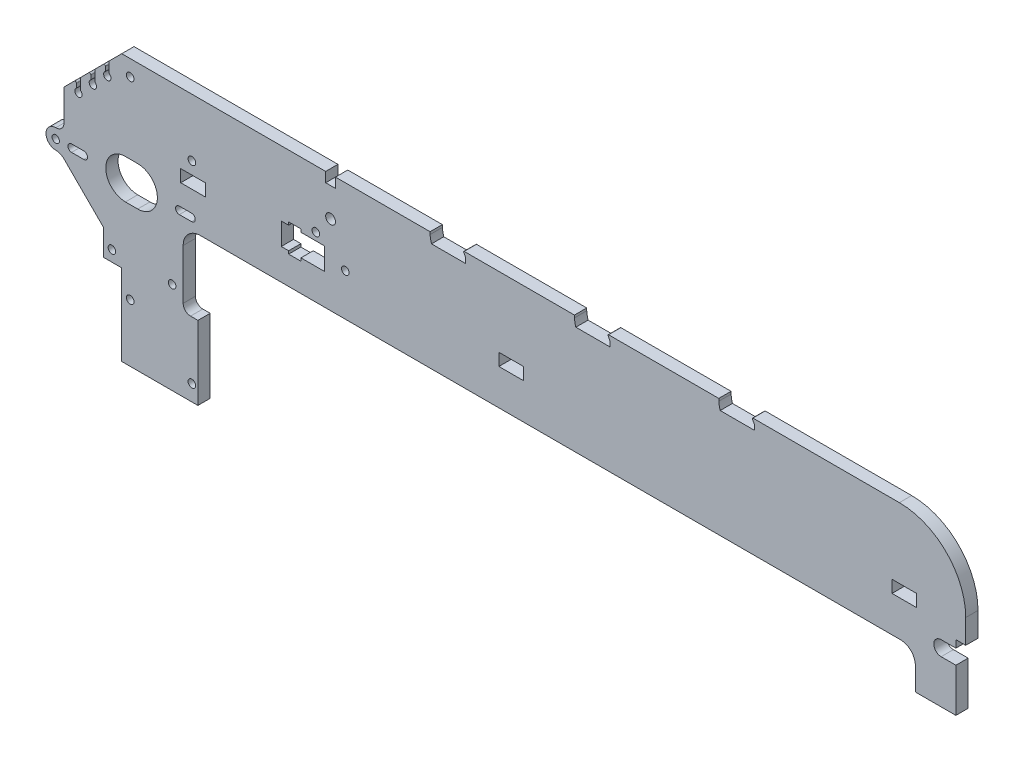
SolidWorks part; units mm, degrees
material "6061-T6 Black anodised"
ref_plane "Front Plane" through (0, 0, 0) normal (0, 0, 1) x (1, 0, 0)
ref_plane "Top Plane" through (0, 0, 0) normal (0, 1, 0) x (1, 0, 0)
ref_plane "Right Plane" through (0, 0, 0) normal (1, 0, 0) x (0, 0, -1)
sketch "Sketch1" plane through (0, 0, 0) normal (0, 0, 1) x (1, 0, 0)
  line L0 (-19.5, 0) -> (36.1968, 0) construction
  line L1 (-1.5, 32) -> (20.5, 32) construction
  line L2 (-21.9203, 0) -> (-30, 0) construction
  line L3 (-6.5, 43.5) -> (-6.5, 28.8553) construction
  line L4 (-1.5, 43.5) -> (20.5, 43.5) construction
  line L5 (310, 43.5) -> (250.4045, 43.5)
  line L6 (21.9203, 0) -> (0, 21.9203) construction
  line L7 (0, 21.9203) -> (-21.9203, 0) construction
  line L8 (-21.9203, 0) -> (0, -21.9203) construction
  line L9 (0, -21.9203) -> (21.9203, 0) construction
  line L10 (316.5, -4.6) -> (316.5, -20)
  line L11 (-6.5, -65) -> (-6.5, -32)
  line L12 (-30, 5.3553) -> (-30, -5.3553) construction
  line L13 (327, 3.7) -> (333, 3.7)
  line L14 (316.5, -20) -> (333, -20)
  line L15 (18.5, -4.6) -> (316.5, -4.6)
  line L16 (34.5, -11.1) -> (59.432, -11.1) construction
  line L17 (333, 6.7) -> (333, 3.7)
  line L18 (9.5, 43.5) -> (9.5, -35.4767) construction
  line L19 (-1.5, 43.5) -> (20.5, 43.5) construction
  line L20 (-1.5, 43.5) -> (-1.5, 20.5) construction
  line L21 (-6.5, -65) -> (24.5, -65)
  line L22 (-1.5, 20.5) -> (20.5, 20.5) construction
  line L23 (327, -2.3) -> (333, -2.3)
  line L24 (333, -2.3) -> (333, -20)
  line L25 (333, 6.7) -> (337, 6.7)
  line L26 (337, 6.7) -> (337, 16.5)
  line L27 (18.5, -35) -> (18.5, -4.6)
  line L28 (20.5, 43.5) -> (20.5, 20.5) construction
  line L29 (17.5, 15) -> (17.5, 10)
  line L30 (17.5, 15) -> (27.5, 15)
  line L31 (27, 72.5933) -> (67, 72.5933) construction
  line L32 (147, 10) -> (157, 10)
  line L33 (147, 10) -> (147, 15)
  line L34 (17.5, 10) -> (27.5, 10)
  line L35 (27.5, 15) -> (27.5, 10)
  line L36 (147, 15) -> (157, 15)
  line L37 (157, 10) -> (157, 15)
  line L38 (307, 10) -> (317, 10)
  line L39 (307, 10) -> (307, 15)
  line L40 (307, 15) -> (317, 15)
  line L41 (317, 10) -> (317, 15)
  line L42 (27, 72.5933) -> (27, -81.6129) construction
  line L43 (27, -81.6129) -> (67, -81.6129) construction
  line L44 (67, 72.5933) -> (67, -81.6129) construction
  line L45 (-1.5, -52.5) -> (20.5, -52.5) construction
  line L46 (-1.5, -65) -> (20.5, -65) construction
  line L47 (-1.5, -65) -> (-1.5, -42) construction
  line L48 (-1.5, -42) -> (20.5, -42) construction
  line L49 (20.5, -65) -> (20.5, -42) construction
  line L50 (58.4277, 8) -> (61.4277, 8)
  line L51 (27.5, 12.5) -> (63.9277, 12.5) construction
  line L52 (61.4277, 6.8061) -> (66.4277, 6.8061)
  line L53 (61.4277, 6.8061) -> (61.4277, 8)
  line L54 (76, 8) -> (76, 17)
  line L55 (72.5, 20.1) -> (72.5, 7.1) construction
  line L56 (66.4277, 6.8061) -> (66.4277, 8)
  line L57 (66.4277, 8) -> (76, 8)
  line L58 (63.9277, 12.5) -> (76, 12.5) construction
  line L59 (66.4277, 18.1939) -> (61.4277, 18.1939)
  line L60 (66.4277, 6.8061) -> (61.4277, 18.1939) construction
  line L61 (61.4277, 6.8061) -> (66.4277, 18.1939) construction
  line L62 (18.5, -35) -> (24.5, -35)
  line L63 (66.4277, 17) -> (66.4277, 18.1939)
  line L64 (66.4277, 17) -> (76, 17)
  line L65 (61.4277, 17) -> (61.4277, 18.1939)
  line L66 (24.5, -35) -> (24.5, -65)
  line L67 (-14, -21.3553) -> (-30, -5.3553)
  line L68 (-14, -21.3553) -> (-14, -32)
  line L69 (-14, -32) -> (-6.5, -32)
  line L70 (119, 43.5) -> (119, 42.5)
  line L71 (119.5675, 39.5) -> (133.5, 39.5)
  line L72 (177.75, 43.5) -> (177.75, 42.5)
  line L73 (119, 43.5) -> (80.5, 43.5)
  line L74 (-6.5, 28.8553) -> (-30, 5.3553) construction
  line L75 (178.3175, 39.5) -> (192.25, 39.5)
  line L76 (159.788, -14) -> (-14, -14) construction
  line L77 (159.788, -14) -> (159.788, -26) construction
  line L78 (61.4277, 17) -> (58.4277, 17)
  line L79 (159.788, -26) -> (-14, -26) construction
  line L80 (-14, -14) -> (-14, -26) construction
  line L81 (58.4277, 17) -> (58.4277, 8)
  line L82 (159.788, -14) -> (-14, -26) construction
  line L83 (159.788, -26) -> (-14, -14) construction
  line L84 (192.25, 39.5) -> (192.25, 41.5)
  line L85 (192.25, 41.5) -> (191.4309, 43.1382)
  line L86 (236.5, 43.5) -> (236.5, 42.5)
  line L87 (237.0675, 39.5) -> (251, 39.5)
  line L88 (251, 39.5) -> (251, 41.5)
  line L89 (177.75, 43.5) -> (132.9045, 43.5)
  line L90 (251, 41.5) -> (250.1809, 43.1382)
  line L91 (-33.3631, 8.7185) -> (-33.3631, -8.7185) construction
  line L92 (76.5, 27.7514) -> (80.5, 27.7514) construction
  line L93 (133.5, 39.5) -> (133.5, 41.5)
  line L94 (76.5, 43.5) -> (76.5, 39.5)
  line L95 (76.5, 39.5) -> (80.5, 39.5)
  line L96 (80.5, 43.5) -> (80.5, 39.5)
  line L97 (76.5, 43.5) -> (-6.5, 43.5)
  line L98 (-30, 20) -> (-6.5, 43.5)
  line L99 (-30, 20) -> (-30, 7.3254)
  line L100 (133.5, 41.5) -> (132.6809, 43.1382)
  line L101 (119, 43.5) -> (177.75, 43.5) construction
  line L102 (191.6545, 43.5) -> (236.5, 43.5)
  circle A0 centre (9.5, 34.5) radius 1.55 construction
  circle A1 centre (0, 0) radius 15.5 construction
  circle A2 centre (0, 21.9203) radius 1.5 construction
  circle A3 centre (21.9203, 0) radius 1.5
  circle A4 centre (0, -21.9203) radius 1.5 construction
  circle A5 centre (-21.9203, 0) radius 1.5
  circle A6 centre (0, 0) radius 5.5 construction
  arc A7 (337, 16.5) -> (310, 43.5) centre (310, 16.5) ccw
  circle A8 centre (0, 0) radius 8
  circle A9 centre (-3.05, 37) radius 1.55
  circle A10 centre (9.5, -57) radius 1.55 construction
  arc A11 (327, 3.7) -> (327, -2.3) centre (327, 0.7) ccw
  circle A12 centre (72, 0.4) radius 5 construction
  circle A13 centre (22, 38.5) radius 5 construction
  circle A14 centre (22, 38.5) radius 1.5 construction
  circle A15 centre (72, 0.4) radius 1.5 construction
  circle A16 centre (22.05, 20) radius 1.55
  circle A17 centre (-3.05, -41.5) radius 1.55
  circle A18 centre (22.05, -58.5) radius 1.55
  circle A19 centre (81.5, 20.1) radius 1.55 construction
  circle A20 centre (72.5, 20.1) radius 1.55
  circle A21 centre (84.5, 12.5) radius 1.55
  circle A22 centre (-10.5, -27.55) radius 1.55
  arc A23 (-33.3631, 3.9623) -> (-33.3631, -3.9623) centre (-33.3631, 0) ccw
  circle A24 centre (14, -27.55) radius 1.55
  circle A25 centre (-33.3631, 0) radius 1.5
  arc A26 (-33.3631, 3.9623) -> (-30, 7.3254) centre (-33.3631, 7.3254) ccw
  arc A27 (-33.3631, -3.9623) -> (-30, -5.3553) centre (-33.3631, -8.7185) cw
  circle A28 centre (78.5, 27.7514) radius 2
  arc A29 (119, 42.5) -> (119.5675, 39.5) centre (132.5, 43.5) ccw
  arc A30 (132.9045, 43.5) -> (132.6809, 43.1382) centre (132.9045, 43.25) ccw
  arc A31 (177.75, 42.5) -> (178.3175, 39.5) centre (191.25, 43.5) ccw
  arc A32 (191.6545, 43.5) -> (191.4309, 43.1382) centre (191.6545, 43.25) ccw
  arc A33 (236.5, 42.5) -> (237.0675, 39.5) centre (250, 43.5) ccw
  arc A34 (250.4045, 43.5) -> (250.1809, 43.1382) centre (250.4045, 43.25) ccw
  point P18 (26.8692, -2.8293)
  point P19 (26.8692, 2.8293)
  point P108 (58.4277, 12.5)
  point P115 (72.894, -20)
  dimension "D2" = 31
  dimension "D3" = 3
  dimension "D4" = 11
  dimension "D12" = 16
  dimension "D20" = 3.1
  dimension "D22" = 8
  dimension "D25" = 3
  dimension "D28" = 6
  dimension "D32" = 10
  dimension "D38" = 3
  dimension "D14" = 31
  dimension "D41" = 3.1
  dimension "D44" = 9
  dimension "D45" = 3.1
  dimension "D53" = 6
  dimension "D18" = 7.5
  dimension "D57" = 3.1
  dimension "D69" = 4
  dimension "D65" = 0.5
  dimension "D7" = 9
  dimension "D11" = 16.5
  dimension "D17" = 15
  dimension "D8" = 65
  dimension "D9" = 43.5
  dimension "D5" = 9.5
  dimension "D6" = 4.6
  dimension "D10" = 6.5
  dimension "D13" = 337
  dimension "D15" = 23
  dimension "D16" = 25
  dimension "D19" = 30
  dimension "D21" = 9
  dimension "D23" = 21.1
  dimension "D24" = 15.4
  dimension "D26" = 6
  dimension "D27" = 4
  dimension "D29" = 67
  dimension "D30" = 17.5
  dimension "D31" = 40
  dimension "D33" = 5
  dimension "D34" = 10
  dimension "D35" = 20
  dimension "D36" = 180
  dimension "D37" = 22
  dimension "D39" = 5
  dimension "D40" = 12
  dimension "D42" = 11
  dimension "D43" = 6
  dimension "D46" = 3.1
  dimension "D47" = 9
  dimension "D48" = 15
  dimension "D49" = 0.7
  dimension "D50" = 5
  dimension "D51" = 12
  dimension "D52" = 3.5
  dimension "D54" = 4
  dimension "D55" = 12
  dimension "D56" = 20
  dimension "D58" = 4.5
  dimension "D59" = 3
  dimension "D60" = 9
  dimension "D61" = 30
  dimension "D62" = 12.5
  dimension "D63" = 1
  dimension "D64" = 14.5
  dimension "D66" = 1
  dimension "D68" = 4
  dimension "D70" = 6
  dimension "D71" = 2
  dimension "D72" = 58.75
  dimension "D67" = 3
extrude "Boss-Extrude1" add sketch "Sketch1" along normal blind 5
fillet "Fillet1" [suppressed] radius 8
fillet "Fillet2" radius 7 1 edges at (18.5, -4.6, 2.5)
fillet "Fillet3" radius 3 1 edges at (18.5, -35, 2.5)
sketch "Sketch2" plane through (0, 0, 5) normal (0, 0, 1) x (1, 0, 0)
  line L0 (21.9203, 0) -> (16.9203, 0) construction
  line L1 (21.9203, -1.5) -> (16.9203, -1.5)
  line L2 (21.9203, 1.5) -> (16.9203, 1.5)
  line L3 (0, 0) -> (-5, 0) construction
  line L4 (0, -8) -> (-5, -8)
  line L5 (0, 8) -> (-5, 8)
  line L6 (-21.9203, 0) -> (-26.9203, 0) construction
  line L7 (-21.9203, -1.5) -> (-26.9203, -1.5)
  line L8 (-21.9203, 1.5) -> (-26.9203, 1.5)
  arc A0 (21.9203, -1.5) -> (21.9203, 1.5) centre (21.9203, 0) ccw
  arc A1 (16.9203, 1.5) -> (16.9203, -1.5) centre (16.9203, 0) ccw
  arc A2 (0, -8) -> (0, 8) centre (0, 0) ccw
  arc A3 (-5, 8) -> (-5, -8) centre (-5, 0) ccw
  arc A4 (-21.9203, -1.5) -> (-21.9203, 1.5) centre (-21.9203, 0) ccw
  arc A5 (-26.9203, 1.5) -> (-26.9203, -1.5) centre (-26.9203, 0) ccw
  circle A6 centre (21.9203, 0) radius 1.5 construction
  circle A7 centre (0, 0) radius 8 construction
  point P4 (19.4203, 0)
  point P9 (-2.5, 0)
  point P16 (-24.4203, 0)
  dimension "D1" = 5
extrude "Cut-Extrude1" cut sketch "Sketch2" against normal through all
fillet "Fillet4" radius 6 1 edges at (316.5, -4.6, 2.5)
sketch "Sketch3" plane through (0, 0, 5) normal (0, 0, 1) x (1, 0, 0)
  line L0 (-12.375, 32.625) -> (-12.375, 37.625) construction
  line L1 (-13.125, 42.8359) -> (-11.625, 42.8359)
  line L2 (-13.125, 42.8359) -> (-13.125, 33.924)
  line L3 (-6.5, 43.5) -> (-30, 20) construction
  line L4 (-11.625, 42.8359) -> (-11.625, 33.924)
  line L5 (-13.125, 42.8359) -> (-11.625, 33.924) construction
  line L6 (-13.125, 33.924) -> (-11.625, 42.8359) construction
  line L7 (-6.5, 43.5) -> (-12.375, 37.625) construction
  line L8 (-12.375, 37.625) -> (-18.25, 31.75) construction
  line L9 (-18.25, 31.75) -> (-24.125, 25.875) construction
  line L10 (-24.125, 25.875) -> (-30, 20) construction
  line L11 (-17.4, 36.9218) -> (-17.4, 27.9859)
  line L12 (-18.25, 26.75) -> (-18.25, 31.75) construction
  line L13 (-19.1, 36.9218) -> (-17.4, 27.9859) construction
  line L14 (-19.1, 27.9859) -> (-17.4, 36.9218) construction
  line L15 (-19.1, 36.9218) -> (-19.1, 27.9859)
  line L16 (-19.1, 36.9218) -> (-17.4, 36.9218)
  line L17 (-23.275, 31.0468) -> (-23.275, 22.1109)
  line L18 (-24.975, 31.0468) -> (-23.275, 22.1109) construction
  line L19 (-24.975, 22.1109) -> (-23.275, 31.0468) construction
  line L20 (-24.975, 31.0468) -> (-23.275, 31.0468)
  line L21 (-24.125, 20.875) -> (-24.125, 25.875) construction
  line L22 (-24.975, 31.0468) -> (-24.975, 22.1109)
  arc A0 (-13.125, 33.924) -> (-11.625, 33.924) centre (-12.375, 32.625) ccw
  arc A1 (-19.1, 27.9859) -> (-17.4, 27.9859) centre (-18.25, 26.75) ccw
  arc A2 (-24.975, 22.1109) -> (-23.275, 22.1109) centre (-24.125, 20.875) ccw
  point P0 (-12.375, 38.3799)
  point P15 (-18.25, 32.4539)
  point P22 (-24.125, 26.5789)
  dimension "D1" = 1.5
  dimension "D2" = 1.5
  dimension "D3" = 5
extrude "Cut-Extrude2" cut sketch "Sketch3" against normal through all
fillet "Fillet5" radius 0.5 3 edges at (-24.975, 25.025, 2.5) (-19.1, 30.9, 2.5) (-13.125, 36.875, 2.5)
equation "\"y-plate-thickness\"=5"
equation "\"bed-plate-thickness\"=3"
equation "\"x-plate-thickness\"=5"
equation "\"D1@Boss-Extrude1\"=\"x-plate-thickness\""
equation "\"D33@Sketch1\"=\"x-plate-thickness\""
